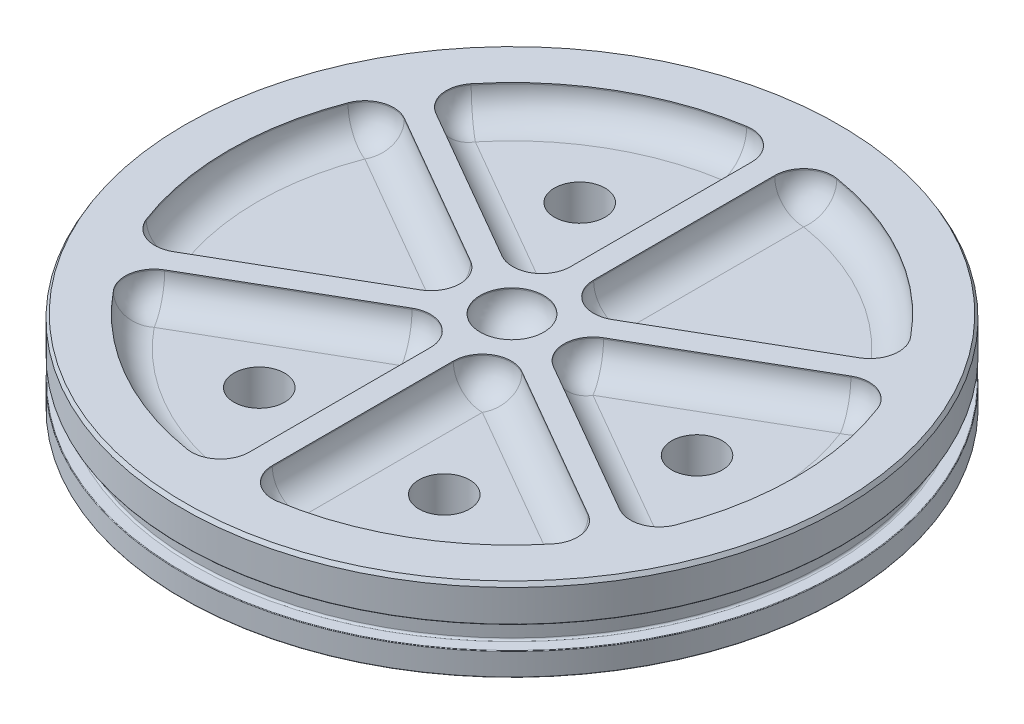
SolidWorks part; units mm, degrees
material "6061-T6 (SS)"
ref_plane "Front Plane" through (0, 0, 0) normal (0, 0, 1) x (1, 0, 0)
ref_plane "Top Plane" through (0, 0, 0) normal (0, 1, 0) x (1, 0, 0)
ref_plane "Right Plane" through (0, 0, 0) normal (1, 0, 0) x (0, 0, -1)
sketch "Sketch1" plane through (0, 0, 0) normal (0, 0, 1) x (1, 0, 0)
  line L0 (0, 48.1922) -> (0, -25.6743) construction
  line L1 (0, 0) -> (72.39, 0)
  line L2 (72.39, 0) -> (72.39, 5.08)
  line L3 (72.39, 5.08) -> (69.469, 5.08)
  line L4 (69.469, 5.08) -> (69.469, 10.0584)
  line L5 (69.469, 10.0584) -> (72.39, 10.0584)
  line L6 (72.39, 10.0584) -> (72.39, 18.034)
  line L7 (72.39, 18.034) -> (62.23, 18.034)
  line L8 (62.23, 18.034) -> (62.23, 11.43)
  line L9 (62.23, 11.43) -> (0, 11.43)
  line L10 (0, 11.43) -> (0, 0)
  dimension "D1" = 144.78
  dimension "D2" = 4.9784
  dimension "D3" = 2.921
  dimension "D5" = 11.43
  dimension "D6" = 10.16
  dimension "D4" = 18.034
  dimension "D7" = 5.08
revolve "Revolve1" add sketch "Sketch1" angle 360 about L0
sketch "Sketch6" plane through (0, 0, 0) normal (0, -1, 0) x (1, 0, 0)
  circle A0 centre (0, 0) radius 65.405
  dimension "D1" = 130.81
extrude "Boss-Extrude1" add sketch "Sketch6" along normal blind 2.54
hole_wizard "Pipe Tap Drill for 1/4 Tap - GN2" positions "Sketch2" profile "Sketch3" hole size "1/4" standard "ANSI Inch" end condition through all
sketch "Sketch2" plane through (0, 11.43, 0) normal (0, 1, 0) x (1, 0, 0)
  line L3 (-20.32, 35.1953) -> (0, 0) construction
  line L4 (0, 0) -> (40.64, 0) construction
  line L6 (0, 0) -> (20.32, -35.1953) construction
  line L7 (0, 0) -> (0, 62.23) construction
  line L8 (0, 0) -> (0, -62.23) construction
  line L9 (0, 0) -> (-20.32, -35.1953) construction
  circle A0 centre (0, 0) radius 62.23 construction
  circle A1 centre (0, 0) radius 62.23 construction
  point P41 (20.32, -35.1953)
  point P44 (-20.32, 35.1953)
  point P47 (40.64, 0)
  point P73 (-20.32, -35.1953)
  dimension "D1" = 40.64
  dimension "D2" = 40.64
  dimension "D3" = 40.64
  dimension "D4" = 30
  dimension "D5" = 30
  dimension "D6" = 30
  dimension "D7" = 40.64
sketch "Sketch3" plane through (20.32, 11.43, 35.1953) normal (1, 0, 0) x (0, 0, 1)
  line L0 (0, 0) -> (0, 13.97)
  line L1 (0, 13.97) -> (5.5626, 13.97)
  line L2 (5.5626, 13.97) -> (5.5626, 0)
  line L5 (5.5626, 0) -> (0, 0)
  line L11 (0, -6.35) -> (0, 107.95) construction
  dimension "Thru Hole Dia." = 11.1252
  dimension "Thru Hole Depth" = 13.97
fillet "CNC ID Fillet" radius 0.4064 3 edges at (-69.469, 10.0584, 0) (-69.469, 5.08, 0) (65.405, 0, 0)
fillet "CNC OD Fillet" radius 0.127 4 edges at (-72.39, 10.0584, 0) (-72.39, 5.08, 0) (65.405, -2.54, 0) (-72.39, 0, 0)
chamfer "CNC Chamfers" distance 0.508 angle 60 1 edges at (-72.39, 18.034, 0)
sketch "Sketch7" plane through (0, 18.034, 0) normal (0, 1, 0) x (1, 0, 0)
  line L0 (0, 0) -> (53.8928, -31.115) construction
  line L1 (0, 0) -> (0, -62.23) construction
  line L2 (0, 0) -> (-53.8928, -31.115) construction
  line L3 (0, 0) -> (-53.8928, 31.115) construction
  line L4 (0, 0) -> (0, 62.23) construction
  line L5 (0, 0) -> (53.8928, 31.115) construction
  line L6 (2.54, 15.3979) -> (2.54, 62.23)
  line L7 (-12.065, 9.8987) -> (-52.6228, 33.3147)
  line L8 (-14.605, -5.4993) -> (-55.1628, -28.9153)
  line L9 (-2.54, -15.3979) -> (-2.54, -62.23)
  line L10 (12.065, -9.8987) -> (52.6228, -33.3147)
  line L11 (14.605, 5.4993) -> (55.1628, 28.9153)
  line L12 (-2.54, 15.3979) -> (-2.54, 62.23)
  line L13 (-14.605, 5.4993) -> (-55.1628, 28.9153)
  line L14 (-12.065, -9.8987) -> (-52.6228, -33.3147)
  line L15 (2.54, -15.3979) -> (2.54, -62.23)
  line L16 (14.605, -5.4993) -> (55.1628, -28.9153)
  line L17 (12.065, 9.8987) -> (52.6228, 33.3147)
  line L18 (2.54, 0) -> (2.54, 62.23) construction
  line L19 (-1.27, 2.1997) -> (52.6228, 33.3147) construction
  line L20 (1.27, -2.1997) -> (55.1628, 28.9153) construction
  line L21 (1.27, 2.1997) -> (55.1628, -28.9153) construction
  line L22 (-1.27, -2.1997) -> (52.6228, -33.3147) construction
  line L23 (2.54, 0) -> (2.54, -62.23) construction
  line L24 (-2.54, 0) -> (-2.54, -62.23) construction
  line L25 (1.27, -2.1997) -> (-52.6228, -33.3147) construction
  line L26 (-1.27, 2.1997) -> (-55.1628, -28.9153) construction
  line L27 (-1.27, -2.1997) -> (-55.1628, 28.9153) construction
  line L28 (1.27, 2.1997) -> (-52.6228, 33.3147) construction
  line L29 (-2.54, 0) -> (-2.54, 62.23) construction
  line L30 (0, 0) -> (-62.23, 0) construction
  circle A0 centre (0, 0) radius 62.23 construction
  circle A1 centre (0, 0) radius 62.23
  arc A2 (2.54, 15.3979) -> (12.065, 9.8987) centre (8.89, 15.3979) ccw
  arc A3 (14.605, 5.4993) -> (14.605, -5.4993) centre (17.78, 0) ccw
  arc A4 (12.065, -9.8987) -> (2.54, -15.3979) centre (8.89, -15.3979) ccw
  arc A5 (-2.54, -15.3979) -> (-12.065, -9.8987) centre (-8.89, -15.3979) ccw
  arc A6 (-14.605, -5.4993) -> (-14.605, 5.4993) centre (-17.78, 0) ccw
  arc A7 (-12.065, 9.8987) -> (-2.54, 15.3979) centre (-8.89, 15.3979) ccw
  circle A9 centre (0, 0) radius 6.985
  point P11 (0, 0)
  circle M5 centre (0, 0) radius 62.23
  dimension "D4" = 6.35
  dimension "D6" = 13.97
  dimension "D5" = 30
  dimension "D2" = 2.54
  dimension "D3" = 2.54
  dimension "D1" = 6
extrude "Boss-Extrude2" add sketch "Sketch7" against normal up to surface (6.604 mm away) contours A7 L7 L13 A6 L8 L14 A5 L9 L15 A4 L10 L16 A3 L11 L17 A2 L6 L12 M5
fillet "Fillet1" radius 6.35 37 edges at (32.3214, 11.43, 21.5937) (5.715, 11.43, 9.8987) (34.8614, 11.43, -17.1943) (11.43, 11.43, 0) (-32.3214, 11.43, -21.5937) (-5.715, 11.43, -9.8987) (-5.715, 11.43, 9.8987) (-2.54, 11.43, 38.788) (-31.115, 11.43, 53.8928) (-32.3214, 11.43, 21.5937) (-11.43, 11.43, 0) (-34.8614, 11.43, 17.1943) (-62.23, 11.43, 0) (-34.8614, 11.43, -17.1943) (5.715, 11.43, -9.8987) (2.54, 11.43, -38.788) (31.115, 11.43, -53.8928) (32.3214, 11.43, -21.5937) (52.5779, 14.732, 33.2888) (2.54, 14.732, 62.1781) (31.115, 11.43, 53.8928) (2.54, 11.43, 38.788) (62.23, 11.43, 0) (34.8614, 11.43, 17.1943) (55.1179, 14.732, 28.8894) (55.1179, 14.732, -28.8894) (52.5779, 14.732, -33.2888) (2.54, 14.732, -62.1781) (-2.54, 14.732, 62.1781) (-52.5779, 14.732, 33.2888) (-55.1179, 14.732, 28.8894) (-52.5779, 14.732, -33.2888) (-2.54, 11.43, -38.788) (-2.54, 14.732, -62.1781) (-31.115, 11.43, -53.8928) (-55.1179, 14.732, -28.8894) (6.985, 11.43, 0)
sketch "Sketch8" plane through (0, -2.54, 0) normal (0, -1, 0) x (1, 0, 0)
  line L2 (-49.0472, -25.3844) -> (-14.605, -5.4993)
  line L3 (-14.605, 5.4993) -> (-49.0472, 25.3844)
  line L4 (-49.0472, -25.3844) -> (-14.605, -5.4993)
  line L5 (-14.605, 5.4993) -> (-49.0472, 25.3844)
  line L6 (-2.54, 15.3979) -> (-2.54, 55.1683)
  line L7 (-46.5072, 29.7839) -> (-12.065, 9.8987)
  line L8 (-2.54, 15.3979) -> (-2.54, 55.1683)
  line L9 (-46.5072, 29.7839) -> (-12.065, 9.8987)
  line L10 (12.065, 9.8987) -> (46.5072, 29.7839)
  line L11 (2.54, 55.1683) -> (2.54, 15.3979)
  line L12 (12.065, 9.8987) -> (46.5072, 29.7839)
  line L13 (2.54, 55.1683) -> (2.54, 15.3979)
  line L14 (14.605, -5.4993) -> (49.0472, -25.3844)
  line L15 (49.0472, 25.3844) -> (14.605, 5.4993)
  line L16 (14.605, -5.4993) -> (49.0472, -25.3844)
  line L17 (49.0472, 25.3844) -> (14.605, 5.4993)
  line L18 (2.54, -15.3979) -> (2.54, -55.1683)
  line L19 (46.5072, -29.7839) -> (12.065, -9.8987)
  line L20 (2.54, -15.3979) -> (2.54, -55.1683)
  line L21 (46.5072, -29.7839) -> (12.065, -9.8987)
  line L22 (-12.065, -9.8987) -> (-46.5072, -29.7839)
  line L23 (-2.54, -55.1683) -> (-2.54, -15.3979)
  line L24 (-12.065, -9.8987) -> (-46.5072, -29.7839)
  line L25 (-2.54, -55.1683) -> (-2.54, -15.3979)
  circle A0 centre (0, 0) radius 6.985 construction
  circle A1 centre (0, 0) radius 65.278
  circle A3 centre (0, 0) radius 6.985
  circle A5 centre (0, 0) radius 65.278
  arc A6 (-58.1565, 22.1449) -> (-58.1565, -22.1449) centre (0, 0) ccw
  arc A8 (-14.605, -5.4993) -> (-14.605, 5.4993) centre (-17.78, 0) ccw
  arc A12 (-14.605, -5.4993) -> (-14.605, 5.4993) centre (-17.78, 0) ccw
  arc A14 (-2.54, 55.1683) -> (-9.9002, 61.4374) centre (-8.89, 55.1683) ccw
  arc A16 (46.5072, 29.7839) -> (48.2563, 39.2926) centre (43.3322, 35.2831) ccw
  arc A17 (-12.065, 9.8987) -> (-2.54, 15.3979) centre (-8.89, 15.3979) ccw
  arc A21 (-12.065, 9.8987) -> (-2.54, 15.3979) centre (-8.89, 15.3979) ccw
  arc A23 (49.0472, -25.3844) -> (58.1565, -22.1449) centre (52.2222, -19.8852) ccw
  arc A25 (2.54, 15.3979) -> (12.065, 9.8987) centre (8.89, 15.3979) ccw
  arc A29 (2.54, 15.3979) -> (12.065, 9.8987) centre (8.89, 15.3979) ccw
  arc A30 (2.54, -55.1683) -> (9.9002, -61.4374) centre (8.89, -55.1683) ccw
  arc A32 (-46.5072, -29.7839) -> (-48.2563, -39.2926) centre (-43.3322, -35.2831) ccw
  arc A33 (14.605, 5.4993) -> (14.605, -5.4993) centre (17.78, 0) ccw
  arc A37 (14.605, 5.4993) -> (14.605, -5.4993) centre (17.78, 0) ccw
  arc A41 (12.065, -9.8987) -> (2.54, -15.3979) centre (8.89, -15.3979) ccw
  arc A45 (12.065, -9.8987) -> (2.54, -15.3979) centre (8.89, -15.3979) ccw
  arc A46 (-58.1565, 22.1449) -> (-58.1565, -22.1449) centre (0, 0) ccw
  arc A47 (-58.1565, -22.1449) -> (-49.0472, -25.3844) centre (-52.2222, -19.8852) ccw
  arc A48 (-58.1565, -22.1449) -> (-49.0472, -25.3844) centre (-52.2222, -19.8852) ccw
  arc A49 (-2.54, -15.3979) -> (-12.065, -9.8987) centre (-8.89, -15.3979) ccw
  arc A53 (-2.54, -15.3979) -> (-12.065, -9.8987) centre (-8.89, -15.3979) ccw
  arc A54 (-49.0472, 25.3844) -> (-58.1565, 22.1449) centre (-52.2222, 19.8852) ccw
  arc A55 (-49.0472, 25.3844) -> (-58.1565, 22.1449) centre (-52.2222, 19.8852) ccw
  arc A56 (-2.54, 55.1683) -> (-9.9002, 61.4374) centre (-8.89, 55.1683) ccw
  arc A57 (-9.9002, 61.4374) -> (-48.2563, 39.2926) centre (0, 0) ccw
  arc A58 (-9.9002, 61.4374) -> (-48.2563, 39.2926) centre (0, 0) ccw
  arc A59 (-48.2563, 39.2926) -> (-46.5072, 29.7839) centre (-43.3322, 35.2831) ccw
  arc A60 (-48.2563, 39.2926) -> (-46.5072, 29.7839) centre (-43.3322, 35.2831) ccw
  arc A61 (46.5072, 29.7839) -> (48.2563, 39.2926) centre (43.3322, 35.2831) ccw
  arc A62 (48.2563, 39.2926) -> (9.9002, 61.4374) centre (0, 0) ccw
  arc A63 (48.2563, 39.2926) -> (9.9002, 61.4374) centre (0, 0) ccw
  arc A64 (9.9002, 61.4374) -> (2.54, 55.1683) centre (8.89, 55.1683) ccw
  arc A65 (9.9002, 61.4374) -> (2.54, 55.1683) centre (8.89, 55.1683) ccw
  arc A66 (49.0472, -25.3844) -> (58.1565, -22.1449) centre (52.2222, -19.8852) ccw
  arc A67 (58.1565, -22.1449) -> (58.1565, 22.1449) centre (0, 0) ccw
  arc A68 (58.1565, -22.1449) -> (58.1565, 22.1449) centre (0, 0) ccw
  arc A69 (58.1565, 22.1449) -> (49.0472, 25.3844) centre (52.2222, 19.8852) ccw
  arc A70 (58.1565, 22.1449) -> (49.0472, 25.3844) centre (52.2222, 19.8852) ccw
  arc A71 (2.54, -55.1683) -> (9.9002, -61.4374) centre (8.89, -55.1683) ccw
  arc A72 (9.9002, -61.4374) -> (48.2563, -39.2926) centre (0, 0) ccw
  arc A73 (9.9002, -61.4374) -> (48.2563, -39.2926) centre (0, 0) ccw
  arc A74 (48.2563, -39.2926) -> (46.5072, -29.7839) centre (43.3322, -35.2831) ccw
  arc A75 (48.2563, -39.2926) -> (46.5072, -29.7839) centre (43.3322, -35.2831) ccw
  arc A76 (-46.5072, -29.7839) -> (-48.2563, -39.2926) centre (-43.3322, -35.2831) ccw
  arc A77 (-48.2563, -39.2926) -> (-9.9002, -61.4374) centre (0, 0) ccw
  arc A78 (-48.2563, -39.2926) -> (-9.9002, -61.4374) centre (0, 0) ccw
  arc A79 (-9.9002, -61.4374) -> (-2.54, -55.1683) centre (-8.89, -55.1683) ccw
  arc A80 (-9.9002, -61.4374) -> (-2.54, -55.1683) centre (-8.89, -55.1683) ccw
  dimension "D1" = 0
  dimension "D2" = 0
  dimension "D3" = 0
  dimension "D4" = 0
  dimension "D5" = 0
  dimension "D6" = 0
  dimension "D7" = 0
extrude "Cut-Extrude1" cut sketch "Sketch8" against normal blind 3.81 contours L8 A56 A58 A60 L9 A21 | L4 A12 L5 A55 A46 A48 | L24 A76 A78 A80 L25 A53 | L20 A71 A73 A75 L21 A45 | L16 A66 A68 A70 L17 A37 | L12 A61 A63 A65 L13 A29 | A3
fillet "Fillet2" radius 6.35 37 edges at (54.3499, 1.27, 25.8681) (62.23, 1.27, 0) (54.3499, 1.27, -25.8681) (31.8261, 1.27, -15.4419) (11.43, 1.27, 0) (4.7725, 1.27, 60.0024) (31.115, 1.27, 53.8928) (49.5774, 1.27, 34.1343) (29.2861, 1.27, 19.8413) (5.715, 1.27, 9.8987) (-5.715, 1.27, -9.8987) (-2.54, 1.27, -35.2831) (-4.7725, 1.27, -60.0024) (-31.115, 1.27, -53.8928) (-49.5774, 1.27, -34.1343) (29.2861, 1.27, -19.8413) (49.5774, 1.27, -34.1343) (31.115, 1.27, -53.8928) (4.7725, 1.27, -60.0024) (2.54, 1.27, -35.2831) (5.715, 1.27, -9.8987) (-29.2861, 1.27, 19.8413) (-49.5774, 1.27, 34.1343) (-31.115, 1.27, 53.8928) (-4.7725, 1.27, 60.0024) (-2.54, 1.27, 35.2831) (-5.715, 1.27, 9.8987) (-31.8261, 1.27, 15.4419) (-11.43, 1.27, 0) (-31.8261, 1.27, -15.4419) (-54.3499, 1.27, -25.8681) (-62.23, 1.27, 0) (-54.3499, 1.27, 25.8681) (31.8261, 1.27, 15.4419) (2.54, 1.27, 35.2831) (-29.2861, 1.27, -19.8413) (6.985, 1.27, 0)
sketch "Sketch9" plane through (0, 18.034, 0) normal (0, 1, 0) x (1, 0, 0)
  circle A0 centre (0, 0) radius 64.9299 construction
  text T0 "THIS SIDE IN                                                               FUEL BULKHEAD                                                                           RELEVANT EXPERIENCE                                "
sketch "Sketch11" plane through (0, 1.27, 0) normal (0, -1, 0) x (1, 0, 0)
  arc A0 (-43.7432, -35.6178) -> (-8.9743, -55.6917) centre (0, 0) ccw construction
  arc A1 (52.7176, -20.0738) -> (52.7176, 20.0738) centre (0, 0) ccw construction
  arc A2 (43.7432, 35.6178) -> (8.9743, 55.6917) centre (0, 0) ccw construction
  arc A3 (-43.7432, -35.6178) -> (-8.9743, -55.6917) centre (0, 0) ccw construction
  arc A4 (52.7176, -20.0738) -> (52.7176, 20.0738) centre (0, 0) ccw construction
  arc A5 (43.7432, 35.6178) -> (8.9743, 55.6917) centre (0, 0) ccw construction
  arc A6 (50.3438, -19.17) -> (50.3438, 19.17) centre (0, 0) ccw construction
  arc A7 (41.7736, 34.0141) -> (8.5702, 53.184) centre (0, 0) ccw construction
  arc A8 (-41.7736, -34.0141) -> (-8.5702, -53.184) centre (0, 0) ccw construction
  text T0 "FILL" font "Century Gothic" height in points 18
  text T1 "GN2" font "Century Gothic" height in points 18
  text T2 "VENT" font "Century Gothic" height in points 18
  dimension "D1" = 2.54
sketch "Sketch12" plane through (0, -2.54, 0) normal (0, -1, 0) x (1, 0, 0)
  line L0 (0, 0) -> (0, 64.9299) construction
  line L1 (1.397, 0) -> (1.397, 64.9299) construction
  circle A0 centre (0, 0) radius 64.9299 construction
  text T0 "THIS SIDE OUT" font "Century Gothic" height in points 11
  dimension "D1" = 1.397
equation "\"D3@Sketch1\"=(5.7-5.47)/2"
